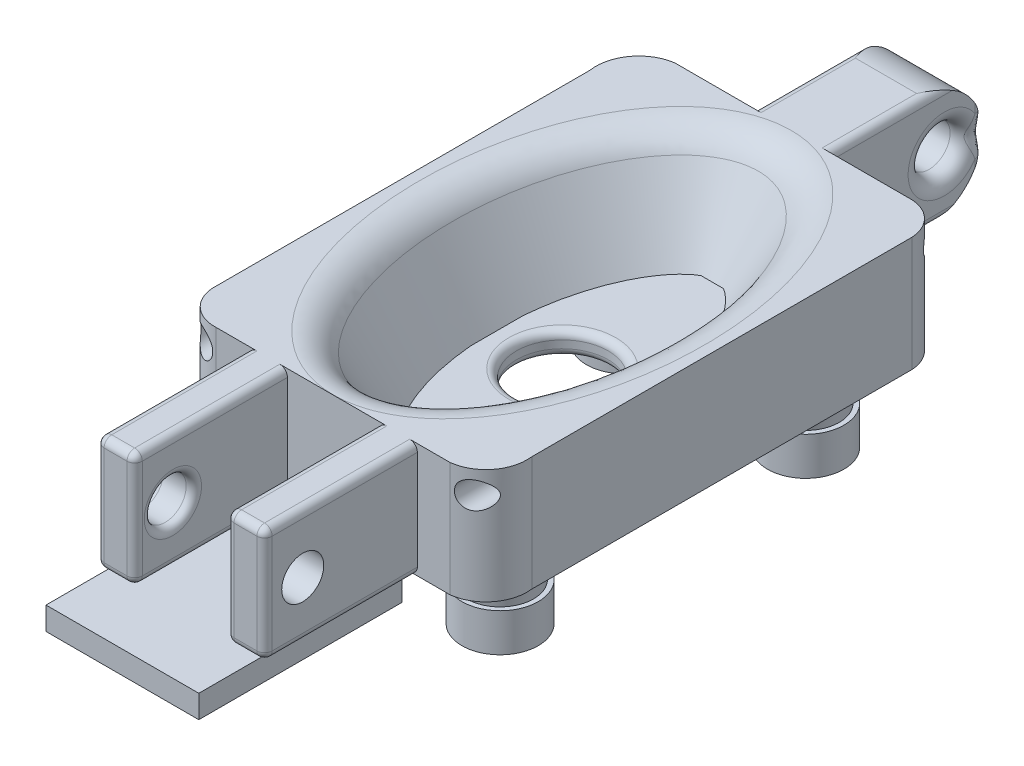
SolidWorks part; units mm, degrees
ref_plane "Front Plane" through (0, 0, 0) normal (0, 0, 1) x (1, 0, 0)
ref_plane "Top Plane" through (0, 0, 0) normal (0, 1, 0) x (1, 0, 0)
ref_plane "Right Plane" through (0, 0, 0) normal (1, 0, 0) x (0, 0, -1)
sketch "Sketch1" plane through (0, 0, 0) normal (0, 1, 0) x (1, 0, 0)
  line L1 (-15.3125, -30) -> (15.3125, -30)
  line L2 (-20, -25.7813) -> (-20, 23.5937)
  line L3 (-15.3125, 30) -> (15.3125, 30)
  line L4 (20, -24.0015) -> (20, 25.7812)
  line L5 (-20, -30) -> (20, 30) construction
  line L6 (-20, 30) -> (20, -30) construction
  arc A0 (-15.3125, 30) -> (-20, 23.5937) centre (-14.4531, 24.4531) ccw
  arc A1 (15.3125, 30) -> (20, 25.7812) centre (15.5469, 25.5469) cw
  arc A2 (15.3125, -30) -> (20, -24.0015) centre (14.657, -24.657) ccw
  arc A3 (-15.3125, -30) -> (-20, -25.7813) centre (-15.5469, -25.5469) cw
  point P0 (0, 0)
  dimension "D1" = 40
  dimension "D2" = 60
extrude "Boss-Extrude1" add sketch "Sketch1" along normal blind 15
sketch "Sketch2" plane through (0, 0, 30) normal (0, 0, 1) x (1, 0, 0)
  line L0 (-20, 15) -> (-20, 0) construction
  line L1 (20.0401, 0) -> (20.0401, 15) construction
  line L2 (15.3125, 0) -> (20.0401, 0) construction
  line L3 (-20, 0) -> (-15.3125, 0) construction
  circle A0 centre (-17.5, 12) radius 1.75
  circle A1 centre (17.5401, 12) radius 1.75
  dimension "D1" = 2.5
  dimension "D5" = 3.5
  dimension "D6" = 3.5
  dimension "D2" = 2.5
  dimension "D3" = 12
  dimension "D4" = 12
sketch "Sketch4" plane through (0, 15, 0) normal (0, 1, 0) x (1, 0, 0)
  ellipse E0 centre (0, 0) end of major axis (0, 27.1105) minor radius 15.7856
extrude "Cut-Extrude6" cut sketch "Sketch4" against normal blind 15 draft 30.5
fillet "Fillet4" radius 5 1 edges at (-2.7969, 15, -26.6816)
extrude "Cut-Extrude7" cut sketch "Sketch2" against normal blind 150
sketch "Sketch5" plane through (0, 0, 0) normal (0, -1, 0) x (1, 0, 0)
  line L1 (7.7139, -19.6019) -> (-8.5645, -19.6019)
  line L2 (7.7139, -19.6019) -> (7.7139, 20.1727)
  line L3 (7.7139, 20.1727) -> (-8.5645, 20.1727)
  line L4 (-8.5645, -19.6019) -> (-8.5645, 20.1727)
extrude "Boss-Extrude2" add sketch "Sketch5" against normal blind 3
sketch "Sketch6" plane through (0, 3, 0) normal (0, 1, 0) x (1, 0, 0)
  circle A0 centre (0, 0) radius 6
extrude "Cut-Extrude8" cut sketch "Sketch6" against normal blind 3
sketch "Sketch8" plane through (0, 0, -30) normal (0, 0, -1) x (-1, 0, 0)
  line L7 (-5, 15) -> (5, 15)
  line L8 (-5, 15) -> (-5, 0)
  line L9 (-5, 0) -> (5, 0)
  line L10 (5, 15) -> (5, 0)
  point P9 (0, 7.5)
extrude "Boss-Extrude3" add sketch "Sketch8" along normal blind 20
sketch "Sketch10" plane through (-5, 0, 0) normal (-1, 0, 0) x (0, 0, 1)
  line L0 (-50, 0) -> (-50, 15) construction
  line L1 (-50, 15) -> (-30, 15) construction
  circle A0 centre (-45, 7.32) radius 2.75
  dimension "D1" = 5
  dimension "D3" = 5.5
  dimension "D2" = 7.68
extrude "Cut-Extrude9" cut sketch "Sketch10" against normal blind 20
fillet "Fillet8" radius 2 1 edges at (5, 4.57, -45)
fillet "Fillet9" radius 1 1 edges at (-5, 4.57, -45)
fillet "Fillet11" radius 1 1 edges at (0, 15, -50)
fillet "Fillet12" radius 1 3 edges at (-5, 15, -39.5) (-5, 14.7071, -49.7071) (-5, 7, -50)
fillet "Fillet13" radius 1 3 edges at (5, 7, -50) (5, 15, -39.5) (5, 14.7071, -49.7071)
fillet "Fillet14" radius 1 5 edges at (-5, 0, -39.5) (-4.7071, 0, -49.7071) (5, 0, -39.5) (0, 0, -50) (4.7071, 0, -49.7071)
sketch "Sketch11" plane through (0, 0, 30) normal (0, 0, 1) x (1, 0, 0)
  line L3 (-10.98, 0) -> (-5.98, 0)
  line L10 (6.02, 0) -> (11.02, 0)
  line L15 (-5.98, 15) -> (-5.98, 0)
  line L20 (6.02, 15) -> (6.02, 0)
  line L25 (6.02, 0) -> (11.02, 0)
  line L26 (6.02, 0) -> (6.02, 15)
  line L27 (6.02, 15) -> (11.02, 15)
  line L28 (11.02, 0) -> (11.02, 15)
  line L30 (-5.98, 15) -> (-10.98, 15)
  line L31 (-5.98, 15) -> (-5.98, 0)
  line L32 (-5.98, 0) -> (-10.98, 0)
  line L33 (-10.98, 15) -> (-10.98, 0)
  point P7 (0.02, 7.5)
  line M22 (-15.3125, 0) -> (15.3125, 0)
  line M24 (15.3125, 15) -> (-15.3125, 15)
  dimension "D7" = 5
extrude "Boss-Extrude4" add sketch "Sketch11" along normal blind 20 contours L33 L15 M24 M22 | L28 L20 M22 M24
sketch "Sketch12" plane through (-10.98, 0, 0) normal (-1, 0, 0) x (0, 0, 1)
  line L0 (50, 0) -> (50, 15) construction
  line L1 (50, 15) -> (30, 15) construction
  circle A0 centre (45, 7.32) radius 2.75
  dimension "D1" = 5
  dimension "D3" = 5.5
  dimension "D2" = 7.68
extrude "Cut-Extrude10" cut sketch "Sketch12" against normal blind 250
fillet "Fillet17" radius 1 1 edges at (-10.98, 4.57, 45)
fillet "Fillet18" radius 1 1 edges at (-5.98, 7.32, 42.25)
fillet "Fillet19" radius 1 1 edges at (-5.98, 0, 40)
fillet "Fillet20" radius 1 3 edges at (-5.98, 8, 50) (-8.98, 0, 50) (-6.2729, 0.2929, 50)
fillet "Fillet21" radius 1 3 edges at (-10.98, 8, 50) (-10.98, 0, 39.5) (-10.98, 0.2929, 49.7071)
fillet "Fillet22" radius 1 5 edges at (-5.98, 15, 39.5) (-8.48, 15, 50) (-6.2729, 15, 49.7071) (-10.98, 15, 39.5) (-10.6871, 15, 49.7071)
fillet "Fillet23" radius 1 1 edges at (6.02, 0, 40)
fillet "Fillet25" radius 1 3 edges at (6.02, 8, 50) (9.02, 0, 50) (6.3129, 0.2929, 50)
fillet "Fillet26" radius 1 3 edges at (11.02, 0, 39.5) (11.02, 8, 50) (11.02, 0.2929, 49.7071)
fillet "Fillet27" radius 1 5 edges at (6.02, 15, 39.5) (6.3129, 15, 49.7071) (11.02, 15, 39.5) (8.52, 15, 50) (10.7271, 15, 49.7071)
fillet "Fillet28" radius 1 1 edges at (6.02, 7.32, 42.25)
fillet "Fillet29" radius 1 1 edges at (0, 0, 6)
fillet "Fillet30" radius 1 1 edges at (0, 3, 6)
sketch "Sketch13" plane through (0, 0, 0) normal (0, -1, 0) x (1, 0, 0)
  line L0 (-20, -23.5937) -> (-20, 25.7813) construction
  line L1 (20, 24.0015) -> (20, -25.7812) construction
  circle A0 centre (-11.8492, 20) radius 5
  circle A1 centre (11.85, 20) radius 5
  circle A2 centre (-11.8492, -20) radius 5
  circle A3 centre (11.85, -20) radius 5
  dimension "D1" = 10
  dimension "D4" = 10
  dimension "D7" = 10
  dimension "D8" = 10
  dimension "D2" = 8.1508
  dimension "D3" = 20
  dimension "D5" = 8.15
  dimension "D6" = 20
  dimension "D9" = 8.1508
  dimension "D10" = 8.15
  dimension "D11" = 20
  dimension "D12" = 20
extrude "Boss-Extrude5" add sketch "Sketch13" along normal blind 5 draft 7
sketch "Sketch14" plane through (0, -5, 0) normal (0, -1, 0) x (1, 0, 0)
  circle A0 centre (-11.8492, 20) radius 5
  circle A1 centre (11.85, 20) radius 5
  circle A2 centre (11.85, -20) radius 5
  circle A3 centre (-11.8492, -20) radius 5
  dimension "D1" = 10
  dimension "D2" = 10
  dimension "D3" = 10
  dimension "D4" = 10
extrude "Boss-Extrude6" add sketch "Sketch14" along normal blind 5
sketch "Sketch19" plane through (0, 0, 0) normal (0, -1, 0) x (1, 0, 0)
  line L0 (10.02, 30) -> (10.02, 49) construction
  line L2 (-9.98, 49) -> (-9.98, 31)
  line L3 (-9.98, 31) -> (10.02, 31)
  line L4 (10.02, 49) -> (10.02, 31)
  line L8 (10.02, 49) -> (10.02, 57.6029)
  line L9 (10.02, 57.6029) -> (-9.98, 57.6029)
  line L10 (-9.98, 49) -> (-9.98, 57.6029)
  dimension "D1" = 18
extrude "Boss-Extrude14" add sketch "Sketch19" along normal blind 3
sketch "Sketch24" plane through (-5, 0, 0) normal (-1, 0, 0) x (0, 0, 1)
  line L0 (-49, 15) -> (-30, 15) construction
  line L1 (-30, 0) -> (-49, 0) construction
  line L3 (-42.0784, 15) -> (-50.6216, 15)
  line L5 (-42.0784, -0.0041) -> (-50.6216, -0.0041)
  line L6 (-50.6216, 15) -> (-50.6216, -0.0041)
  arc A1 (-50.0388, 7.32) -> (-42.0784, 15) centre (-42.2186, 7.1798) cw
  arc A2 (-42.2186, 0) -> (-50.0388, 7.32) centre (-42.4687, 7.5701) cw
  line M3 (-49, 14) -> (-49, 1)
  line M4 (-49, 1) -> (-30, 1)
  line M6 (-30, 14) -> (-49, 14)
  dimension "D1" = 8.5432
extrude "Cut-Extrude11" cut sketch "Sketch24" against normal blind 25 contours A1 M3 M6 | A2 A1 L3 L6 L5 M3 M6 M4 | A2 M4 M3
